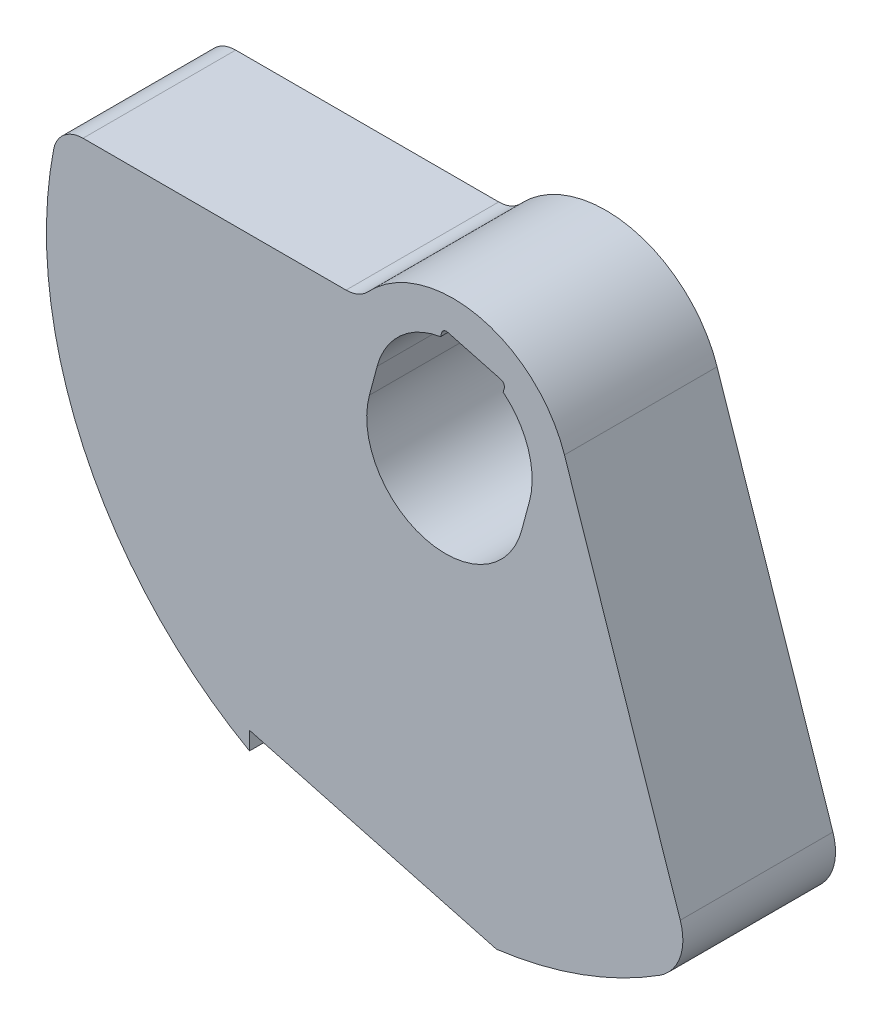
SolidWorks part; units mm, degrees
ref_plane "Front Plane" through (0, 0, 0) normal (0, 0, 1) x (1, 0, 0)
ref_plane "Top Plane" through (0, 0, 0) normal (0, 1, 0) x (1, 0, 0)
ref_plane "Right Plane" through (0, 0, 0) normal (1, 0, 0) x (0, 0, -1)
sketch "Sketch1" plane through (0, 0, 0) normal (0, 0, 1) x (1, 0, 0)
  line L0 (0, 40.7088) -> (0, -42.4788) construction
  line L1 (50.0011, 0) -> (-47.9361, 0) construction
  line L2 (0, 0) -> (4.815, 17.9697) construction
  line L3 (-7.4706, 2.0017) -> (6.4814, -1.7367) construction
  line L4 (-7.0762, 3.4738) -> (6.8758, -0.2646) construction
  line L5 (-3.8765, 1.0387) -> (-3.482, 2.5108)
  line L6 (4.2709, 0.4334) -> (3.8765, -1.0387)
  line L7 (-5.0653, 5.08) -> (-18.4566, 5.08)
  line L8 (6.0531, 3.3717) -> (7.0281, 0.4672)
  line L9 (12.9403, -3.6173) -> (17.147, -10.9034)
  line L10 (0, 0) -> (5.8427, -10.1199) construction
  line L11 (0, 0) -> (43.883, -11.7584) construction
  line L12 (12.7, 40.7088) -> (12.7, -42.4788) construction
  line L13 (50.0011, -9.398) -> (-47.9361, -9.398) construction
  line L14 (-1.0387, -3.8765) -> (-9.0244, -1.7367) construction
  line L15 (-9.9822, -16.7843) -> (-9.9822, -17.6991)
  line L16 (-9.9822, -16.7843) -> (2.5931, -20.1539)
  line L17 (2.8088, 5.0851) -> (0.11, 5.8082)
  line L18 (1.4594, 5.4467) -> (-6.5263, 7.5864) construction
  line L21 (2.9359, 4.578) -> (2.9884, 4.774)
  line L24 (-0.2536, 5.4326) -> (-0.2011, 5.6286)
  arc A0 (-3.8765, 1.0387) -> (3.8765, -1.0387) centre (0, 0) ccw
  arc A1 (6.1601, -0.0728) -> (6.1791, 0) centre (0.3944, 1.4721) ccw
  arc A2 (4.2709, 0.4334) -> (2.9359, 4.578) centre (0.3944, 1.4721) ccw
  arc A3 (7.0281, 0.4672) -> (12.6001, -3.4269) centre (12.446, 2.286) ccw
  arc A4 (6.0531, 3.3717) -> (-3.9548, 5.5602) centre (0.3944, 1.4721) ccw
  arc A5 (-19.953, 3.8443) -> (-9.9822, -17.6991) centre (0, 0) ccw
  arc A6 (12.6001, -3.4269) -> (12.9403, -3.6173) centre (12.6104, -3.8078) cw
  arc A7 (2.5931, -20.1539) -> (17.147, -10.9034) centre (0, 0) ccw
  arc A8 (-18.4566, 5.08) -> (-19.953, 3.8443) centre (-18.4566, 3.556) ccw
  arc A9 (-5.0653, 5.08) -> (-3.9548, 5.5602) centre (-5.0653, 6.604) ccw
  circle A10 centre (12.7, -9.398) radius 1.1938
  arc A11 (-0.2536, 5.4326) -> (-3.482, 2.5108) centre (0.3944, 1.4721) ccw
  arc A12 (2.8088, 5.0851) -> (2.9884, 4.774) centre (2.7431, 4.8397) cw
  arc A13 (-0.2011, 5.6286) -> (0.11, 5.8082) centre (0.0443, 5.5629) cw
  point P35 (-9.9822, 40.7088)
  point P36 (-9.9822, -42.4788)
  point P48 (1.5947, -0.4273)
  point P50 (6.4097, 17.5424)
  point P51 (-1.5947, 0.4273)
  point P52 (3.2202, 18.397)
  dimension "D1" = 8.0264
  dimension "D4" = 11.938
  dimension "D6" = 11.43
  dimension "D11" = 40.64
  dimension "D12" = 0.381
  dimension "D16" = 1.524
  dimension "D17" = 1.524
  dimension "D20" = 2.3876
  dimension "D24" = 0.254
  dimension "D2" = 15
  dimension "D5" = 5.08
  dimension "D7" = 2.286
  dimension "D8" = 12.446
  dimension "D9" = 60
  dimension "D10" = 9.398
  dimension "D13" = 15
  dimension "D14" = 18.796
  dimension "D15" = 9.9822
  dimension "D22" = 3.302
  dimension "D23" = 1.651
  dimension "D3" = 1.524
  dimension "D18" = 12.7
  dimension "D19" = 9.398
  dimension "D21" = 9.652
extrude "Boss-Extrude1" add sketch "Sketch1" against normal blind 7.7724 contours A9 L7 A8 A5 L15 L16 A7 L9 A6 A3 L8 A4 A10 A2 L6 A0 L5 region at (-3.0537, -7.1996, 0)
sketch "Sketch2" plane through (0, 0, 0) normal (0, 0, 1) x (1, 0, 0)
  line L0 (7.0281, 0.4672) -> (12.5499, -15.9813)
  arc A0 (2.5931, -20.1539) -> (17.147, -10.9034) centre (0, 0) ccw construction
extrude "Cut-Extrude1" cut sketch "Sketch2" against normal through all and the other way through all
fillet "Fillet1" radius 2.54 1 edges at (12.5499, -15.9813, -3.8862)
